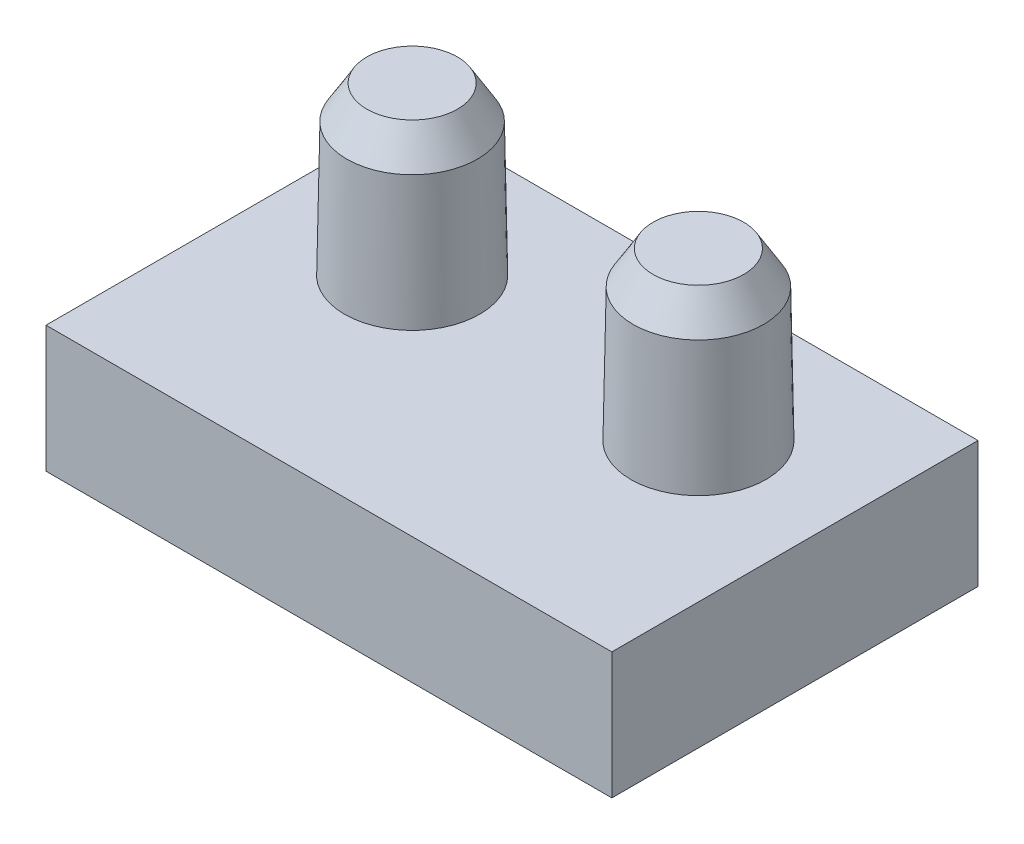
SolidWorks part; units mm, degrees
note: The reader was unsure of these and kept them because the rebuilt part matched: shared geometry of "Sketch2<2>".
ref_plane "Front Plane" through (0, 0, 0) normal (0, 0, 1) x (1, 0, 0)
ref_plane "Top Plane" through (0, 0, 0) normal (0, 1, 0) x (1, 0, 0)
ref_plane "Right Plane" through (0, 0, 0) normal (1, 0, 0) x (0, 0, -1)
sketch "Sketch1" plane through (0, 0, 0) normal (0, 1, 0) x (1, 0, 0)
  line L0 (0, 2.75) -> (0, -2.75) construction
  line L1 (-4.25, 2.75) -> (4.25, 2.75)
  line L2 (-4.25, 2.75) -> (-4.25, -2.75)
  line L3 (-4.25, -2.75) -> (4.25, -2.75)
  line L4 (4.25, 2.75) -> (4.25, -2.75)
  point P6 (0, 0)
  dimension "D1" = 8.5
  dimension "D2" = 5.5
extrude "Boss-Extrude1" add sketch "Sketch1" along normal blind 1.9
sketch "Sketch2" plane through (0, 1.9, 0) normal (0, 1, 0) x (1, 0, 0)
  line L0 (-2.15, 0.65) -> (2.15, 0.65) construction
  line L1 (0, 0.65) -> (0, -2.75) construction
  line L2 (-4.25, -2.75) -> (4.25, -2.75) construction
  circle A0 centre (-2.15, 0.65) radius 1
  circle A1 centre (2.15, 0.65) radius 1
  dimension "D3" = 2
  dimension "D1" = 3.4
  dimension "D2" = 4.3
extrude "Boss-Extrude2" add sketch "Sketch2" against normal up to body draft 1 from offset 0.9 separate body draft outward yes
extrude "Boss-Extrude3" add sketch "Sketch2<2>" along normal offset from surface 4.4 draft 1 from surface at 0.9
sketch "Sketch2<2>" plane through (0, 1.9, 0) normal (0, 1, 0) x (1, 0, 0) same geometry as "Sketch2"
chamfer "Chamfer1" distance 0.5 angle 30 2 edges at (2.15, 4.4, 0.3221) (-2.15, 4.4, 0.3221)
